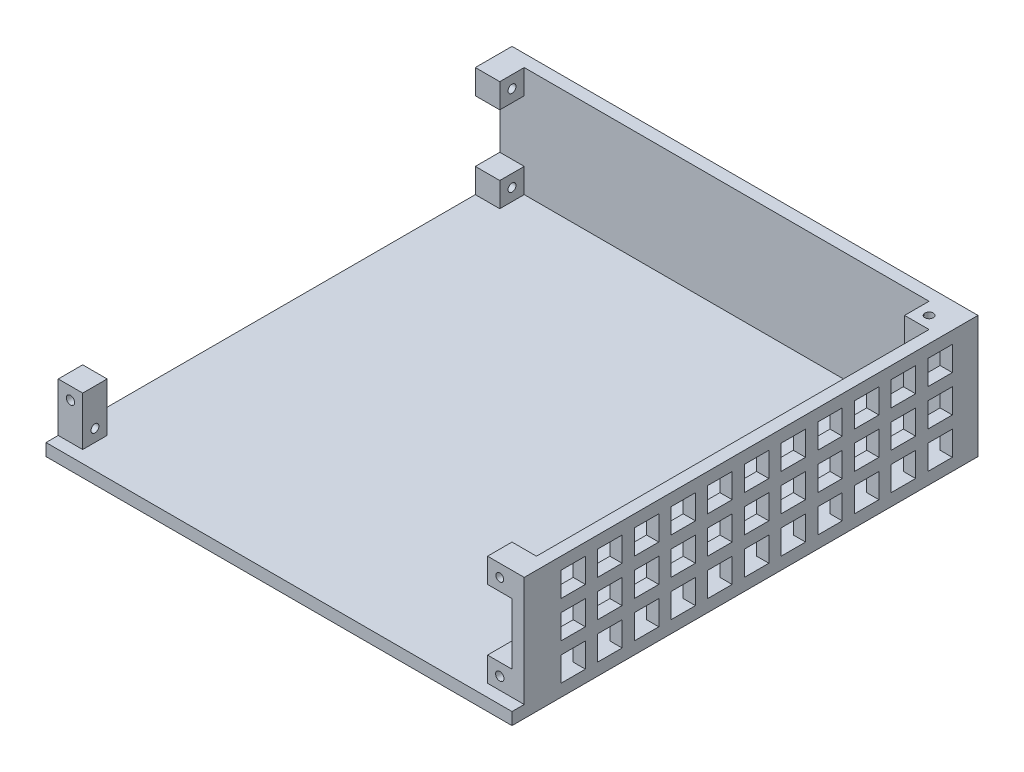
SolidWorks part; units mm, degrees
ref_plane "Front Plane" through (0, 0, 0) normal (0, 0, 1) x (1, 0, 0)
ref_plane "Top Plane" through (0, 0, 0) normal (0, 1, 0) x (1, 0, 0)
ref_plane "Right Plane" through (0, 0, 0) normal (1, 0, 0) x (0, 0, -1)
sketch "Sketch1" plane through (0, 0, 0) normal (0, 1, 0) x (1, 0, 0)
  line L1 (-95.25, 95.25) -> (95.25, 95.25)
  line L2 (-95.25, 95.25) -> (-95.25, -95.25)
  line L3 (-95.25, -95.25) -> (95.25, -95.25)
  line L4 (95.25, 95.25) -> (95.25, -95.25)
  line L5 (-95.25, 95.25) -> (95.25, -95.25) construction
  line L6 (-95.25, -95.25) -> (95.25, 95.25) construction
  point P0 (0, 0)
  dimension "D1" = 190.5
  dimension "D2" = 190.5
extrude "Boss-Extrude1" add sketch "Sketch1" along normal blind 5
sketch "Sketch9" plane through (0, 5, 0) normal (0, 1, 0) x (1, 0, 0)
  line L0 (95.25, -95.25) -> (95.25, 95.25) construction
  line L1 (-95.25, 95.25) -> (95.25, 95.25)
  line L2 (-95.25, 95.25) -> (-95.25, 90.25)
  line L3 (-95.25, 90.25) -> (95.25, 90.25)
  line L4 (95.25, 95.25) -> (95.25, 90.25)
  dimension "D1" = 5
extrude "Boss-Extrude5" add sketch "Sketch9" along normal blind 45
sketch "Sketch10" plane through (0, 5, 0) normal (0, 1, 0) x (1, 0, 0)
  line L0 (-95.25, -95.25) -> (95.25, -95.25) construction
  line L1 (95.25, 90.25) -> (90.25, 90.25)
  line L2 (95.25, 90.25) -> (95.25, -95.25)
  line L3 (95.25, -95.25) -> (90.25, -95.25)
  line L4 (90.25, 90.25) -> (90.25, -95.25)
  dimension "D1" = 5
extrude "Boss-Extrude6" add sketch "Sketch10" along normal up to surface (45 mm away) up to face at (0, 50, -92.75)
sketch "Sketch11" plane through (95.25, 0, 0) normal (1, 0, 0) x (0, 0, -1)
  line L0 (-95.25, 50) -> (95.25, 50) construction
  line L1 (-65.25, 45) -> (-75.25, 45)
  line L2 (-65.25, 45) -> (-65.25, 35)
  line L3 (-65.25, 35) -> (-75.25, 35)
  line L4 (-75.25, 45) -> (-75.25, 35)
  line L5 (-95.25, 50) -> (-95.25, 0) construction
  dimension "D1" = 5
  dimension "D2" = 20
  dimension "D3" = 10
  dimension "D4" = 10
extrude "Cut-Extrude3" cut sketch "Sketch11" against normal up to surface (5 mm away) up to face at (90.25, 27.5, 2.5)
pattern_linear "LPattern3" count 3 spacing 15 along (0, -1, 0) of "Cut-Extrude3"
pattern_linear "LPattern4" count 11 spacing 15 along (0, 0, -1) of "LPattern3"
sketch "Sketch12" plane through (-95.25, 0, 0) normal (-1, 0, 0) x (0, 0, 1)
  line L1 (-90.25, 5) -> (-80.25, 5)
  line L2 (-90.25, 5) -> (-90.25, 15)
  line L3 (-90.25, 15) -> (-80.25, 15)
  line L4 (-80.25, 5) -> (-80.25, 15)
  dimension "D1" = 10
  dimension "D2" = 10
extrude "Boss-Extrude7" add sketch "Sketch12" against normal blind 10
mirror "Mirror1" about plane through (0, 0, 0) normal (0, 0, 1) of "Boss-Extrude7"
sketch "Sketch13" plane through (0, 50, 0) normal (0, 1, 0) x (1, 0, 0)
  line L0 (90.25, 90.25) -> (90.25, -95.25) construction
  line L1 (95.25, -95.25) -> (90.25, -95.25)
  line L2 (95.25, -95.25) -> (95.25, -90.25)
  line L3 (95.25, -90.25) -> (90.25, -90.25)
  line L4 (90.25, -95.25) -> (90.25, -90.25)
  dimension "D1" = 5
extrude "Cut-Extrude4" cut sketch "Sketch13" against normal up to surface (45 mm away) up to face at (65.5463, 5, -0.3426)
sketch "Sketch14" plane through (-95.25, 0, 0) normal (-1, 0, 0) x (0, 0, 1)
  line L0 (80.25, 15) -> (90.25, 15) construction
  line L1 (80.25, 5) -> (80.25, 15) construction
  circle A0 centre (85.25, 10) radius 1.625
  point P4 (85.25, 15)
  point P7 (80.25, 10)
  dimension "D1" = 3.25
extrude "Cut-Extrude5" cut sketch "Sketch14" against normal up to surface (10 mm away) up to face at (-85.25, 10, 85.25)
mirror "Mirror2" about plane through (0, 0, 0) normal (0, 0, 1) of "Cut-Extrude5"
sketch "Sketch15" plane through (0, 0, -90.25) normal (0, 0, 1) x (1, 0, 0)
  line L1 (-95.25, 50) -> (-85.25, 50)
  line L2 (-95.25, 50) -> (-95.25, 40)
  line L3 (-95.25, 40) -> (-85.25, 40)
  line L4 (-85.25, 50) -> (-85.25, 40)
  line L5 (90.25, 50) -> (80.25, 50)
  line L6 (90.25, 50) -> (90.25, 40)
  line L7 (90.25, 40) -> (80.25, 40)
  line L8 (80.25, 50) -> (80.25, 40)
  dimension "D1" = 10
  dimension "D2" = 10
extrude "Boss-Extrude8" add sketch "Sketch15" along normal blind 10
sketch "Sketch16" plane through (-95.25, 0, 0) normal (-1, 0, 0) x (0, 0, 1)
  line L0 (-80.25, 50) -> (-80.25, 40) construction
  circle A0 centre (-85.25, 45) radius 1.625
  circle A1 centre (-85.25, 10) radius 1.625 construction
  point P4 (0, 0)
  point P8 (-80.25, 45)
  dimension "D1" = 5
extrude "Cut-Extrude6" cut sketch "Sketch16" against normal up to surface (10 mm away) up to face at (-85.25, 45, -85.25)
sketch "Sketch17" plane through (0, 50, 0) normal (0, 1, 0) x (1, 0, 0)
  line L1 (80.25, 80.25) -> (80.25, 90.25) construction
  line L2 (90.25, 80.25) -> (80.25, 80.25) construction
  circle A0 centre (85.25, 85.25) radius 1.7
  point P2 (0, 0)
  dimension "D1" = 3.4
  dimension "D2" = 5
  dimension "D3" = 5
extrude "Cut-Extrude7" cut sketch "Sketch17" against normal up to surface (10 mm away) up to face at (86.25, 40, -85.15)
sketch "Sketch18" plane through (90.25, 0, 0) normal (-1, 0, 0) x (0, 0, 1)
  line L1 (90.25, 50) -> (80.25, 50)
  line L2 (90.25, 50) -> (90.25, 40)
  line L3 (90.25, 40) -> (80.25, 40)
  line L4 (80.25, 50) -> (80.25, 40)
  dimension "D1" = 10
  dimension "D2" = 10
extrude "Boss-Extrude9" add sketch "Sketch18" along normal blind 10
sketch "Sketch19" plane through (0, 0, 90.25) normal (0, 0, 1) x (1, 0, 0)
  line L0 (80.25, 40) -> (80.25, 50) construction
  line L1 (80.25, 40) -> (90.25, 40) construction
  circle A0 centre (85.25, 45) radius 1.6
  dimension "D1" = 5
  dimension "D2" = 3.2
  dimension "D3" = 5
extrude "Cut-Extrude8" cut sketch "Sketch19" against normal up to surface (10 mm away) up to face at (85.25, 45, 80.25)
sketch "Sketch20" plane through (0, 0, 90.25) normal (0, 0, 1) x (1, 0, 0)
  line L1 (-85.25, 15) -> (-95.25, 15)
  line L2 (-85.25, 15) -> (-85.25, 25)
  line L3 (-85.25, 25) -> (-95.25, 25)
  line L4 (-95.25, 15) -> (-95.25, 25)
  dimension "D1" = 10
  dimension "D2" = 10
extrude "Boss-Extrude10" add sketch "Sketch20" against normal up to surface (10 mm away) up to face at (-90.25, 10, 80.25)
sketch "Sketch21" plane through (0, 0, 90.25) normal (0, 0, 1) x (1, 0, 0)
  line L0 (-85.25, 25) -> (-95.25, 25) construction
  line L1 (-85.25, 25) -> (-85.25, 5) construction
  circle A0 centre (-90.25, 20) radius 1.7
  dimension "D1" = 3.4
  dimension "D2" = 5
  dimension "D3" = 5
extrude "Cut-Extrude9" cut sketch "Sketch21" against normal up to surface (10 mm away) up to face at (-90.25, 15, 80.25)
sketch "Sketch22" plane through (90.25, 0, 0) normal (-1, 0, 0) x (0, 0, 1)
  line L1 (90.25, 5) -> (80.25, 5)
  line L2 (90.25, 5) -> (90.25, 15)
  line L3 (90.25, 15) -> (80.25, 15)
  line L4 (80.25, 5) -> (80.25, 15)
  dimension "D1" = 10
  dimension "D2" = 10
extrude "Boss-Extrude11" add sketch "Sketch22" along normal blind 10
sketch "Sketch23" plane through (0, 0, 90.25) normal (0, 0, 1) x (1, 0, 0)
  line L0 (80.25, 5) -> (80.25, 15) construction
  line L1 (80.25, 15) -> (90.25, 15) construction
  circle A0 centre (85.25, 10) radius 1.7
  dimension "D1" = 3.4
  dimension "D2" = 5
  dimension "D3" = 5
extrude "Cut-Extrude10" cut sketch "Sketch23" against normal up to surface (10 mm away) up to face at (85.25, 10, 80.25)
